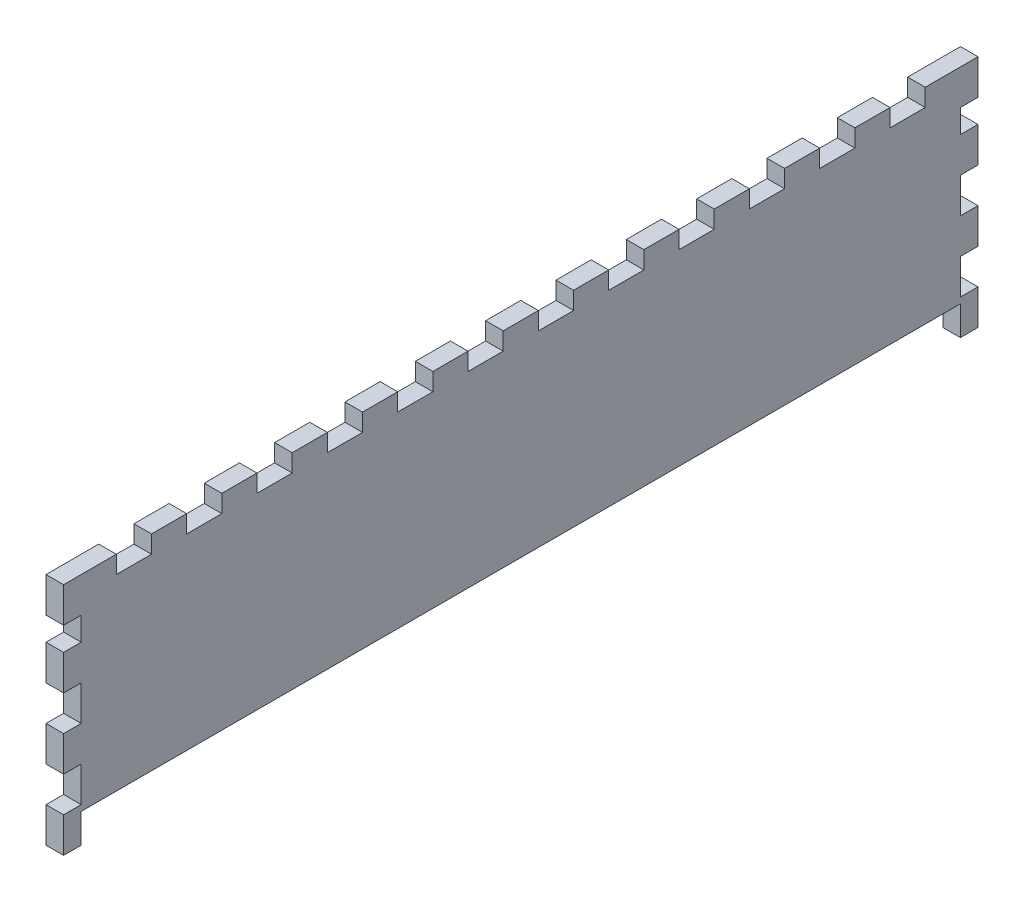
SolidWorks part; units mm, degrees
ref_plane "Front Plane" through (0, 0, 0) normal (0, 0, 1) x (1, 0, 0)
ref_plane "Top Plane" through (0, 0, 0) normal (0, 1, 0) x (1, 0, 0)
ref_plane "Right Plane" through (0, 0, 0) normal (1, 0, 0) x (0, 0, -1)
sketch "Sketch1" plane through (0, 0, 0) normal (1, 0, 0) x (0, 0, -1)
  line L1 (-75, 16) -> (75, 16)
  line L2 (-75, 16) -> (-75, -16)
  line L3 (-75, -16) -> (75, -16)
  line L4 (75, 16) -> (75, -16)
  line L5 (-75, 16) -> (75, -16) construction
  line L6 (-75, -16) -> (75, 16) construction
  point P0 (0, 0)
  dimension "D1" = 150
  dimension "D2" = 32
extrude "Boss-Extrude1" add sketch "Sketch1" along normal blind 3
sketch "Sketch3" plane through (0, 0, -75) normal (0, 0, -1) x (-1, 0, 0)
  line L0 (0, 0) -> (-3, 0) construction
  line L1 (0, -16) -> (0, 16) construction
  line L2 (-3, -16) -> (-3, 16) construction
  line L4 (0, 3) -> (-3, 3)
  line L5 (0, 3) -> (0, 9)
  line L6 (0, 9) -> (-3, 9)
  line L7 (-3, 3) -> (-3, 9)
  line L8 (0, 3) -> (-3, 9) construction
  line L9 (0, 9) -> (-3, 3) construction
  point P10 (-1.5, 6)
  dimension "D1" = 3
  dimension "D2" = 6
extrude "Boss-Extrude2" add sketch "Sketch3" along normal blind 3
pattern_linear "LPattern1" count 3 spacing 12 along (0, -1, 0) count 2 spacing 10 along (0, 1, 0) of "Boss-Extrude2" pattern seed only yes
ref_plane "Plane1" through (0, -16, 0) normal (0, -1, 0) x (-1, 0, 0)
sketch "Sketch4" plane through (0, 16, 0) normal (0, 1, 0) x (1, 0, 0)
  line L0 (0, 0) -> (3, 0) construction
  line L1 (0, 75) -> (0, -75) construction
  line L2 (3, 75) -> (3, -75) construction
  line L4 (0, -3) -> (3, -3)
  line L5 (0, -3) -> (0, 3)
  line L6 (0, 3) -> (3, 3)
  line L7 (3, -3) -> (3, 3)
  line L8 (0, -3) -> (3, 3) construction
  line L9 (0, 3) -> (3, -3) construction
  point P7 (1.5, 0)
  dimension "D1" = 6
extrude "Boss-Extrude3" add sketch "Sketch4" along normal blind 3
pattern_linear "LPattern2" count 7 spacing 12 along (0, 0, -1) count 7 spacing 12 along (0, 0, 1) of "Boss-Extrude3" pattern seed only yes
ref_plane "Plane2" through (0, 0, 0) normal (0, 0, 1) x (1, 0, 0)
mirror "Mirror1" about plane through (0, 0, 0) normal (0, 0, 1) of "LPattern1"
